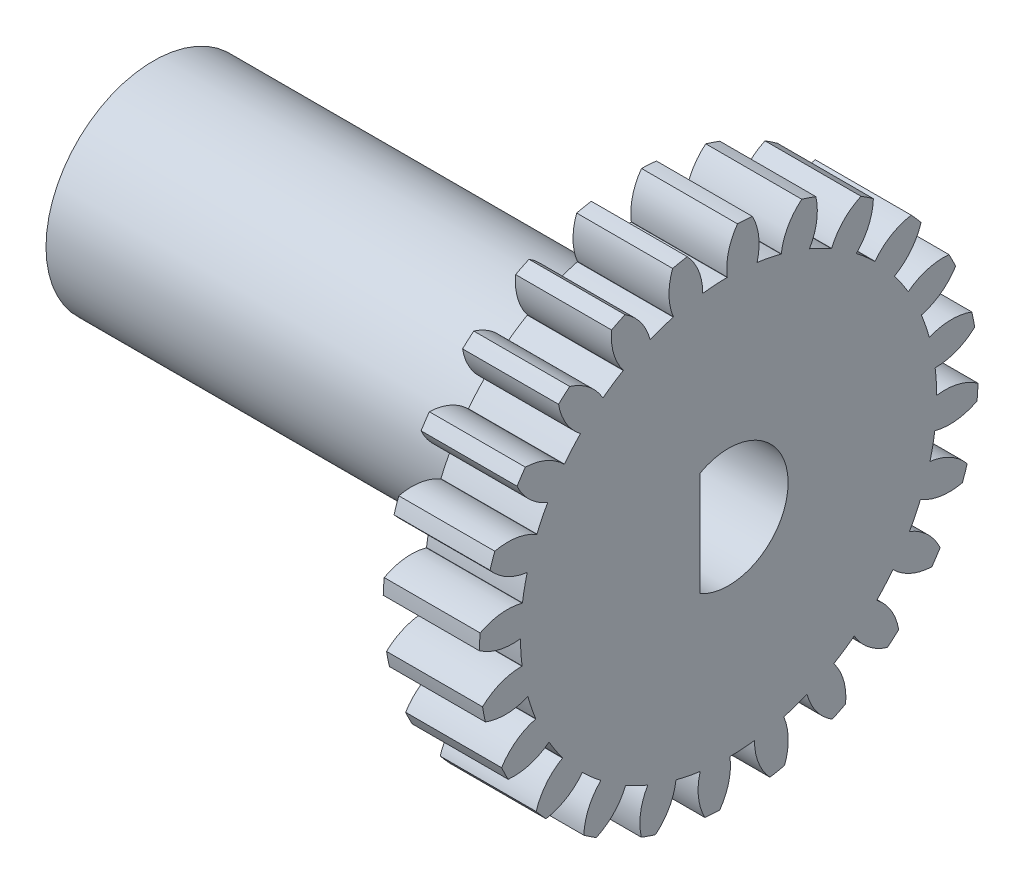
SolidWorks part; units mm, degrees
ref_plane "Front Plane" through (0, 0, 0) normal (0, 0, 1) x (1, 0, 0)
ref_plane "Top Plane" through (0, 0, 0) normal (0, 1, 0) x (1, 0, 0)
ref_plane "Right Plane" through (0, 0, 0) normal (1, 0, 0) x (0, 0, -1)
sketch "Sketch1" plane through (0, 0, 0) normal (1, 0, 0) x (0, 0, -1)
  line L0 (0, 0) -> (0, 13) construction
  line L1 (0, 0) -> (1.6968, 12.8888) construction
  line L2 (-2.9089, 11.2477) -> (0, 12)
  circle A0 centre (0, 0) radius 12 construction
  circle A1 centre (0, 0) radius 13
  circle A2 centre (0, 0) radius 10.843
  circle A3 centre (0, 0) radius 11.6178 construction
  circle A5 centre (2.9044, 11.2489) radius 3
  dimension "D1" = 24
  dimension "D2" = 26
  dimension "D3" = 21.686
  dimension "D6" = 6
  dimension "D4" = 7.5
  dimension "D5" = 75.5
ref_axis "Axis1" through (7.0509, 0, 0) along (-1, 0, 0)
sketch "Sketch2" plane through (0, 0, 0) normal (1, 0, 0) x (0, 0, -1)
  circle A0 centre (0, 0) radius 10.843
  circle A1 centre (0, 0) radius 10.843 construction
extrude "Boss-Extrude1" add sketch "Sketch2" along normal mid plane 5
sketch "Sketch4" plane through (0, 0, 0) normal (1, 0, 0) x (0, 0, -1)
  line L0 (0, 0) -> (0, 13) construction
  line L1 (0, 0) -> (2.1414, 32.6712) construction
  arc A0 (0.8826, 13.4652) -> (0.6106, 9.3154) centre (2.9044, 11.2489) ccw
  circle A1 centre (2.9044, 11.2489) radius 3 construction
  arc A2 (0.8826, 13.4652) -> (0.6106, 9.3154) centre (-1.4113, 11.5317) cw
  dimension "D1" = 3.75
extrude "Boss-Extrude3" add sketch "Sketch4" along normal mid plane 5
sketch "Sketch5" plane through (0, 0, 0) normal (1, 0, 0) x (0, 0, -1)
  circle A0 centre (0, 0) radius 13
  circle A1 centre (0, 0) radius 13 construction
  circle A2 centre (0, 0) radius 38.4
  dimension "D1" = 25.4
extrude "Cut-Extrude1" cut sketch "Sketch5" against normal through all both and the other way through all
fillet "Fillet1" radius 0.01 2 edges at (0, 10.8428, 0.0679) (0, 10.7412, -1.4826)
pattern_circular "CirPattern2" count 24 over 360 about axis through (2.5, 0, 0) along (1, 0, 0) of "Fillet1", "Cut-Extrude1", "Boss-Extrude3"
shell "Shell1" [suppressed] thickness 4.5
sketch "Sketch6" plane through (0, 0, 0) normal (1, 0, 0) x (0, 0, -1)
  circle A0 centre (0, 0) radius 12 construction
  dimension "D1" = 24
sketch "Sketch8" plane through (-2.5, 0, 0) normal (-1, 0, 0) x (0, 0, 1)
  circle A0 centre (0, 0) radius 3.1 construction
  circle A1 centre (0, 0) radius 5.6
  dimension "D1" = 2.5
  dimension "D2" = 6.2
extrude "Boss-Extrude4" add sketch "Sketch8" along normal blind 24.96
sketch "Sketch9" plane through (-27.46, 0, 0) normal (-1, 0, 0) x (0, 0, 1)
  circle A0 centre (0, 0) radius 3.1
  dimension "D1" = 6.2
extrude "Cut-Extrude3" cut sketch "Sketch9" against normal through all
sketch "Sketch10" plane through (-27.46, 0, 0) normal (-1, 0, 0) x (0, 0, 1)
  line L0 (1.5, 2.7129) -> (1.5, -2.7129)
  circle A0 centre (0, 0) radius 3.1 construction
  circle A1 centre (0, 0) radius 3 construction
  arc A2 (1.5, -2.7129) -> (1.5, 2.7129) centre (0, 0) ccw
  arc A3 (1.5, 2.7129) -> (1.5, -2.7129) centre (0, 0) ccw construction
  dimension "D1" = 6
  dimension "D2" = 4.5
extrude "Boss-Extrude5" add sketch "Sketch10" against normal through all from offset 5 offset against normal yes
sketch "Sketch7" plane through (-2.5, 0, 0) normal (-1, 0, 0) x (0, 0, 1)
  line L2 (1.5, 2.5981) -> (1.5, -2.5981) construction
  line L5 (1.6, 2.6552) -> (1.6, -2.6552)
  arc A4 (1.5, 2.5981) -> (1.5, -2.5981) centre (0, 0) ccw construction
  arc A5 (1.5, -2.5981) -> (1.5, 2.5981) centre (0, 0) ccw construction
  arc A6 (1.6, 2.6552) -> (1.6, -2.6552) centre (0, 0) ccw
  circle A7 centre (0, 0) radius 3.1 construction
  dimension "D1" = 6
  dimension "D2" = 4.5
equation "\"N\"= 24"
equation "\"DP\"= 1"
equation "\"PD\"= \"N\" / \"DP\""
equation "\"CP\"= \"PD\" / \"N\" * 3.141"
equation "\"A\"= 1 / \"DP\""
equation "\"D\"= 1.157 / \"DP\""
equation "\"OD\"= \"PD\" + 2 * \"A\""
equation "\"RD\"= \"PD\" - 2 * \"D\""
equation "\"T\"= 5"
equation "\"F\"= .01"
equation "\"D1@Sketch1\"=\"PD\""
equation "\"D1@Boss-Extrude1\"=\"T\""
equation "\"D4@Sketch1\"=360/(\"N\"*2)"
equation "\"D6@Sketch1\"=\"PD\"/4"
equation "\"D3@Sketch1\"=\"RD\""
equation "\"D2@Sketch1\"=\"OD\""
equation "\"D1@Sketch4\"=360/(\"N\"*4)"
equation "\"D1@Boss-Extrude3\"=\"T\""
equation "\"D1@Fillet1\"=\"F\""
equation "\"D1@CirPattern2\"=\"N\""
equation "\"D1@Shell1\"=\"T\"*.9"
equation "\"D1@Sketch6\"=\"PD\""
equation "\"SHAFT_LENGTH\" = 24.96"
equation "\"D1@Boss-Extrude4\"=\"SHAFT_LENGTH\""
